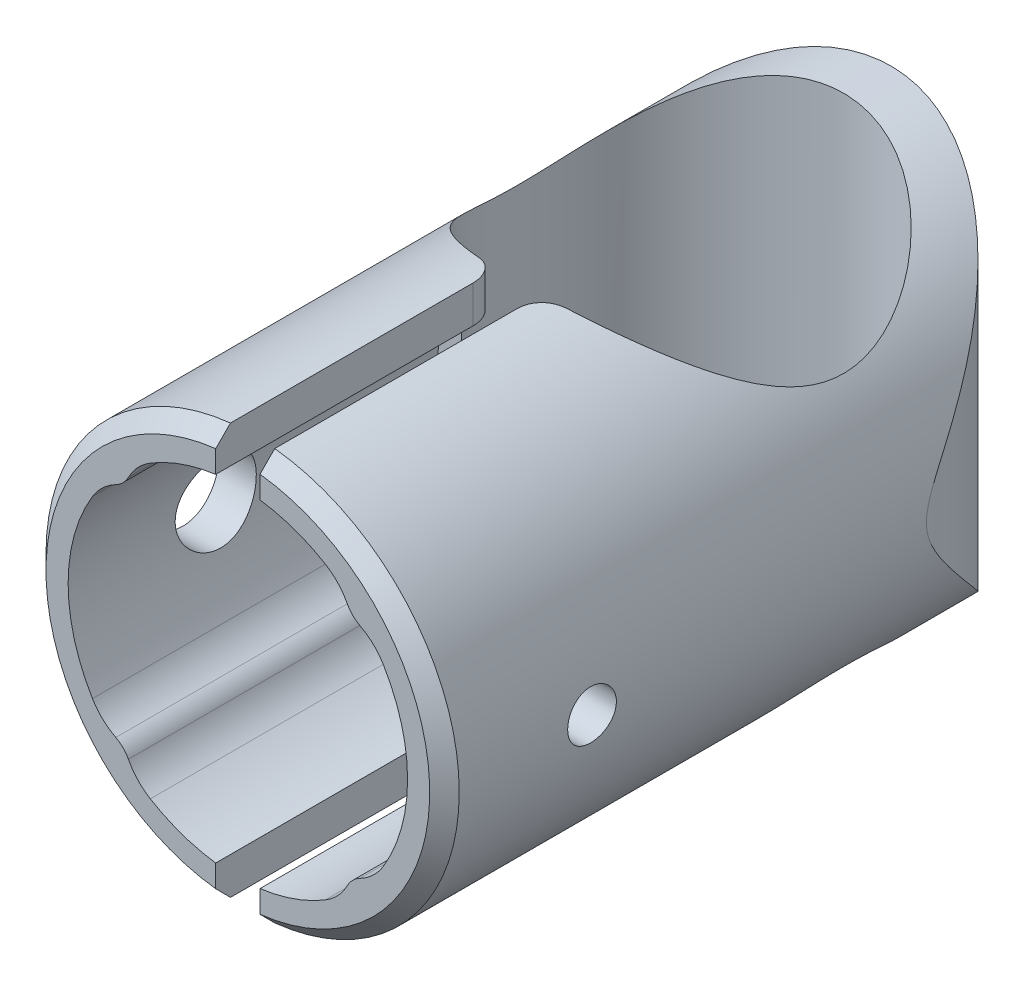
SolidWorks part; units mm, degrees
material "Сплав 2024"
ref_plane "Спереди" through (0, 0, 0) normal (0, 0, 1) x (1, 0, 0)
ref_plane "Сверху" through (0, 0, 0) normal (0, 1, 0) x (1, 0, 0)
ref_plane "Справа" through (0, 0, 0) normal (1, 0, 0) x (0, 0, -1)
sketch "Эскиз1" plane through (0, 0, 0) normal (0, 0, 1) x (1, 0, 0)
  circle A0 centre (0, 0) radius 14
  dimension "D1" = 28
extrude "Бобышка-Вытянуть1" add sketch "Эскиз1" along normal blind 45
ref_plane "Плоскость1" through (0, 14, 0) normal (0, 1, 0) x (1, 0, 0)
sketch "Эскиз2" plane through (0, 14, 0) normal (0, 1, 0) x (1, 0, 0)
  line L0 (0, 0) -> (0, -45) construction
  line L1 (-14, -45) -> (14, -45) construction
  line L2 (14, 0) -> (-14, 0) construction
  line L8 (-1.5, -25.9477) -> (-1.5, -45)
  line L9 (-1.5, -45) -> (1.5, -45)
  line L10 (1.5, -25.9477) -> (1.5, -45)
  line L11 (-1.5, -25.9477) -> (1.5, -45) construction
  line L12 (-1.5, -45) -> (1.5, -25.9477) construction
  arc A0 (1.5, -25.9477) -> (-1.5, -25.9477) centre (0, -15) ccw
  point P9 (0, -12.5)
  point P10 (0, -35.4739)
  point P17 (12.5, -12.5)
  dimension "D1" = 22.1
  dimension "D3" = 3
  dimension "D2" = 15
extrude "Вырез-Вытянуть1" cut sketch "Эскиз2" against normal through all
sketch "Эскиз3" plane through (0, 14, 0) normal (0, 1, 0) x (1, 0, 0)
  line L1 (-14, 0) -> (14, 0)
  line L2 (14, 0) -> (-14, 0) construction
  line L3 (14, 0) -> (14, -12.3425)
  line L4 (-14, 0) -> (-14, -12.3425)
  arc A1 (14, -12.3425) -> (-14, -12.3425) centre (0, -15) ccw
  dimension "D1" = 28.5
extrude "Вырез-Вытянуть2" cut sketch "Эскиз3" against normal through all
mirror "Зеркальное отражение1" [suppressed] about plane through (0, 0, 0) normal (1, 0, 0)
sketch "Эскиз5" plane through (0, 0, 45) normal (0, 0, 1) x (1, 0, 0)
  arc A0 (-9.8521, 5.9318) -> (-9.8521, -5.9318) centre (0, 0) ccw
  arc A1 (-8.27, 7.4178) -> (-7.4178, 8.27) centre (-9.1924, 9.1924) ccw
  arc A2 (-5.9318, 9.8521) -> (-7.4178, 8.27) centre (-3.8686, 6.4253) ccw
  arc A3 (-8.27, 7.4178) -> (-9.8521, 5.9318) centre (-6.4253, 3.8686) ccw
  arc A4 (7.4178, 8.27) -> (5.9318, 9.8521) centre (3.8686, 6.4253) ccw
  arc A5 (9.8521, 5.9318) -> (8.27, 7.4178) centre (6.4253, 3.8686) ccw
  arc A6 (8.27, -7.4178) -> (9.8521, -5.9318) centre (6.4253, -3.8686) ccw
  arc A7 (5.9318, -9.8521) -> (7.4178, -8.27) centre (3.8686, -6.4253) ccw
  arc A8 (-7.4178, -8.27) -> (-5.9318, -9.8521) centre (-3.8686, -6.4253) ccw
  arc A9 (-9.8521, -5.9318) -> (-8.27, -7.4178) centre (-6.4253, -3.8686) ccw
  arc A10 (7.4178, 8.27) -> (8.27, 7.4178) centre (9.1924, 9.1924) ccw
  arc A11 (8.27, -7.4178) -> (7.4178, -8.27) centre (9.1924, -9.1924) ccw
  arc A12 (-7.4178, -8.27) -> (-8.27, -7.4178) centre (-9.1924, -9.1924) ccw
  arc A13 (5.9318, 9.8521) -> (-5.9318, 9.8521) centre (0, 0) ccw
  arc A14 (9.8521, -5.9318) -> (9.8521, 5.9318) centre (0, 0) ccw
  arc A15 (-5.9318, -9.8521) -> (5.9318, -9.8521) centre (0, 0) ccw
  point P30 (-21.4826, 19.4308)
  point P31 (-21.4826, 19.4308)
extrude "Вырез-Вытянуть3" cut sketch "Эскиз5" against normal blind 25
ref_plane "Плоскость2" through (-14, 0, 0) normal (-1, 0, 0) x (0, 0, 1)
sketch "Эскиз7" plane through (-14, 0, 0) normal (-1, 0, 0) x (0, 0, 1)
  line L0 (45, 0) -> (0, 0) construction
  line L1 (45, -13.9194) -> (45, 13.9194) construction
  line L2 (35, 13.9194) -> (35, -13.9194) construction
  line L3 (45, 13.9194) -> (25.9477, 13.9194) construction
  line L4 (25.9477, -13.9194) -> (45, -13.9194) construction
  dimension "D1" = 10
hole_wizard "Отверстие с зазором M51" positions "Эскиз9" profile "Эскиз8" hole size "M5" standard "Ansi Metric"
sketch "Эскиз9" plane through (-14, 0, 0) normal (-1, 0, 0) x (0, 0, 1)
  line L0 (45, 0) -> (0, 0) construction
  line L1 (35, 13.9194) -> (35, -13.9194) construction
  point P0 (35, 0)
sketch "Эскиз8" plane through (-14, 0, 35) normal (0, 1, 0) x (0, 0, 1)
  line L0 (0, 0) -> (0, 6.6524)
  line L1 (0, 6.6524) -> (2.75, 5)
  line L2 (2.75, 5) -> (2.75, 0)
  line L5 (2.75, 0) -> (0, 0)
  line L10 (0, 6.6524) -> (-2.75, 5) construction
  line L11 (0, -6.35) -> (0, 107.95) construction
  dimension "Диаметр отверстия" = 5.5
  dimension "Глубина отверстия" = 5
  dimension "Угол заточки сверла" = 118
ref_plane "Плоскость3" through (14, 0, 0) normal (1, 0, 0) x (0, 0, -1)
hole_wizard "Отверстие обработанное метчиком M4x0.71" positions "Эскиз12" profile "Эскиз11" tap size "M4x0.7" standard "Ansi Metric"
sketch "Эскиз12" plane through (14, 0, 0) normal (1, 0, 0) x (0, 0, -1)
  line L0 (-45, 0) -> (0, 0) construction
  line L1 (-35, 13.9194) -> (-35, -13.9194) construction
  point P0 (-35, 0)
sketch "Эскиз11" plane through (14, 0, 35) normal (0, 1, 0) x (0, 0, -1)
  line L0 (0, 0) -> (0, 12.4914)
  line L1 (0, 12.4914) -> (1.65, 11.5)
  line L2 (1.65, 11.5) -> (1.65, 0)
  line L5 (1.65, 0) -> (0, 0)
  line L10 (0, 12.4914) -> (-1.65, 11.5) construction
  line L11 (0, -6.35) -> (0, 107.95) construction
  dimension "Диаметр сверла" = 3.3
  dimension "Глубина сверла" = 11.5
  dimension "Угол заточки сверла" = 118
cosmetic thread "Отверстие резьбы1" parameters "D1"=3.1245, "D2"=4
chamfer "Фаска1" distance 1 angle 45 2 edges at (14, 0, 45) (-14, 0, 45)
fillet "Скругление1" radius 2 4 edges at (-1.5, -12.6606, 25.9477) (1.5, -12.6606, 25.9477) (1.5, 12.6606, 25.9477) (-1.5, 12.6606, 25.9477)
